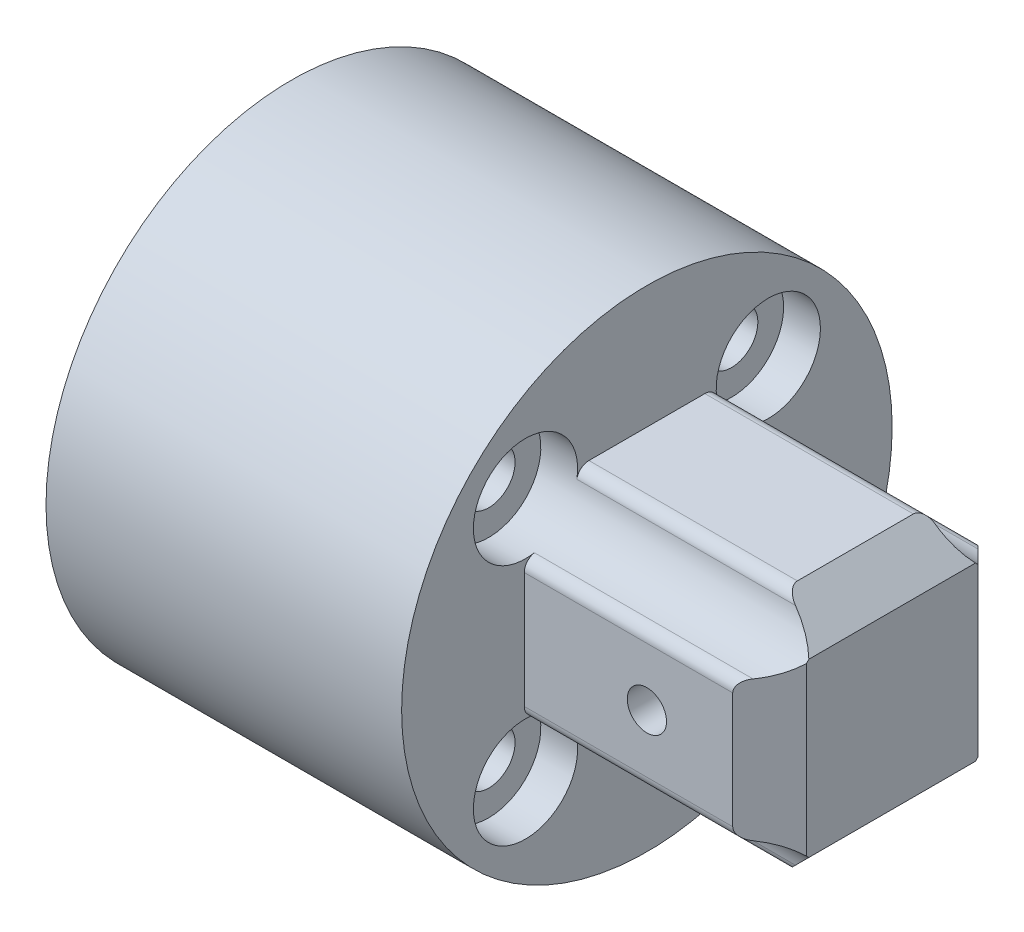
SolidWorks part; units mm, degrees
ref_plane "前视基准面" through (0, 0, 0) normal (0, 0, 1) x (1, 0, 0)
ref_plane "上视基准面" through (0, 0, 0) normal (0, 1, 0) x (1, 0, 0)
ref_plane "右视基准面" through (0, 0, 0) normal (1, 0, 0) x (0, 0, -1)
sketch "草图1" plane through (0, 0, 0) normal (1, 0, 0) x (0, 0, -1)
  circle A0 centre (0, 0) radius 20
  dimension "D1" = 40
extrude "凸台-拉伸1" add sketch "草图1" along normal blind 10
sketch "草图2" plane through (0, 0, 0) normal (-1, 0, 0) x (0, 0, 1)
  line L1 (-7.5, -15.25) -> (7.5, -15.25)
  line L2 (-7.5, -15.25) -> (-7.5, 15.25)
  line L3 (-7.5, 15.25) -> (7.5, 15.25)
  line L4 (7.5, -15.25) -> (7.5, 15.25)
  line L5 (-7.5, -15.25) -> (7.5, 15.25) construction
  line L6 (-7.5, 15.25) -> (7.5, -15.25) construction
  point P0 (0, 0)
  dimension "D1" = 15
  dimension "D2" = 30.5
extrude "切除-拉伸1" cut sketch "草图2" against normal blind 4
sketch "草图3" plane through (4, 0, 0) normal (-1, 0, 0) x (0, 0, 1)
  circle A0 centre (0, 0) radius 8.75
  dimension "D1" = 17.5
extrude "切除-拉伸2" cut sketch "草图3" along normal blind 4
sketch "草图4" plane through (0, 0, 0) normal (-1, 0, 0) x (0, 0, 1)
  line L1 (-9, -16) -> (9, -16)
  line L2 (-9, -16) -> (-9, 16)
  line L3 (-9, 16) -> (9, 16)
  line L4 (9, -16) -> (9, 16)
  line L5 (-9, -16) -> (9, 16) construction
  line L6 (-9, 16) -> (9, -16) construction
  circle A0 centre (0, 0) radius 20
  dimension "D3" = 40
  dimension "D1" = 32
  dimension "D2" = 18
extrude "凸台-拉伸2" add sketch "草图4" along normal blind 19
fillet "圆角1" radius 3 4 edges at (-9.5, -16, -9) (-9.5, -16, 9) (-9.5, 16, -9) (-9.5, 16, 9)
sketch "草图5" plane through (-19, 0, 0) normal (-1, 0, 0) x (0, 0, 1)
  line L0 (-6, -16) -> (6, -16) construction
  line L1 (6, 16) -> (-6, 16) construction
  circle A0 centre (0, -16) radius 2.5
  circle A1 centre (0, 16) radius 2.5
  dimension "D1" = 5
  dimension "D2" = 5
extrude "切除-拉伸3" cut sketch "草图5" against normal blind 20
fillet "圆角2" radius 3 4 edges at (-9.5, -16, -2.5) (-9.5, -16, 2.5) (-9.5, 16, 2.5) (-9.5, 16, -2.5)
sketch "草图6" plane through (10, 0, 0) normal (1, 0, 0) x (0, 0, -1)
  line L0 (0, 0) -> (20, 0) construction
  line L1 (0, 0) -> (18.216, -18.216) construction
  circle A0 centre (0, 0) radius 14 construction
  circle A2 centre (9.8995, -9.8995) radius 2.15
  circle A3 centre (0, 0) radius 14 construction
  circle A4 centre (-9.8995, -9.8995) radius 2.15
  circle A5 centre (0, 0) radius 14 construction
  circle A6 centre (-9.8995, 9.8995) radius 2.15
  circle A7 centre (0, 0) radius 14 construction
  circle A8 centre (9.8995, 9.8995) radius 2.15
  point P21 (0, 0)
  dimension "D1" = 28
  dimension "D3" = 4.3
  dimension "D2" = 45
  dimension "D4" = 4
extrude "切除-拉伸4" cut sketch "草图6" against normal blind 43
fillet "圆角3" radius 1 8 edges at (-9.5, -7.9467, 9) (-9.5, -11.8523, 9) (-9.5, -11.8523, -9) (-9.5, -7.9467, -9) (-9.5, 7.9467, -9) (-9.5, 11.8523, -9) (-9.5, 11.8523, 9) (-9.5, 7.9467, 9)
sketch "草图7" plane through (10, 0, 0) normal (1, 0, 0) x (0, 0, -1)
  circle A0 centre (9.8995, -9.8995) radius 4.25
  dimension "D1" = 8.5
extrude "切除-拉伸5" cut sketch "草图7" against normal blind 3
pattern_circular "阵列(圆周)1" count 4 over 360 about axis through (0, 0, 0) along (1, 0, 0) of "切除-拉伸5"
sketch "草图8" plane through (10, 0, 0) normal (1, 0, 0) x (0, 0, -1)
  line L1 (-10, -10) -> (10, -10)
  line L2 (-10, -10) -> (-10, 10)
  line L3 (-10, 10) -> (10, 10)
  line L4 (10, -10) -> (10, 10)
  line L5 (-10, -10) -> (10, 10) construction
  line L6 (-10, 10) -> (10, -10) construction
  point P0 (0, 0)
  dimension "D1" = 20
  dimension "D2" = 20
extrude "凸台-拉伸3" add sketch "草图8" along normal blind 20
sketch "草图9" plane through (0, 0, -10) normal (0, 0, -1) x (-1, 0, 0)
  line L0 (-10, 20) -> (-10, -20) construction
  circle A0 centre (-20, 0) radius 1.6
  dimension "D1" = 3.2
  dimension "D2" = 10
extrude "切除-拉伸6" cut sketch "草图9" against normal blind 27
chamfer "倒角1" distance 3 angle 45 4 edges at (30, -10, 0) (30, 0, 10) (30, 10, 0) (30, 0, -10)
sketch "草图11" plane through (10, 0, 0) normal (1, 0, 0) x (0, 0, -1)
  circle A0 centre (-9.8995, 9.8995) radius 4.25
  circle A1 centre (-9.8995, -9.8995) radius 4.25
  circle A2 centre (9.8995, -9.8995) radius 4.25
  circle A3 centre (9.8995, 9.8995) radius 4.25
  point P12 (0, 0)
  dimension "D1" = 8.5
  dimension "D2" = 4
extrude "切除-拉伸7" cut sketch "草图11" along normal blind 49
sketch "草图12" plane through (0, -15.25, 0) normal (0, 1, 0) x (1, 0, 0)
  line L1 (1.5, -2.5) -> (-1.5, -2.5)
  line L2 (1.5, -2.5) -> (1.5, 2.5)
  line L3 (1.5, 2.5) -> (-1.5, 2.5)
  line L4 (-1.5, -2.5) -> (-1.5, 2.5)
  line L5 (1.5, -2.5) -> (-1.5, 2.5) construction
  line L6 (1.5, 2.5) -> (-1.5, -2.5) construction
  point P0 (0, 0)
  dimension "D1" = 3
  dimension "D2" = 5
extrude "切除-拉伸8" cut sketch "草图12" against normal blind 49
fillet "圆角4" radius 1 3 edges at (0.75, -15.25, 2.5) (0.75, -15.25, -2.5) (1.5, -15.25, 0)
fillet "圆角5" radius 1 4 edges at (0, -19.8431, 2.5) (1.5, -20, 0) (0, -19.8431, -2.5) (-1.5, -20, 0)
fillet "圆角6" radius 1 7 edges at (18.5, 5.6507, -10) (18.5, 10, -5.6507) (18.5, 10, 5.6507) (18.5, 5.6507, 10) (18.5, -5.6507, 10) (18.5, -10, 5.6507) (18.5, -10, -5.6507)
fillet "圆角7" radius 1 1 edges at (18.5, -5.6507, -10)
